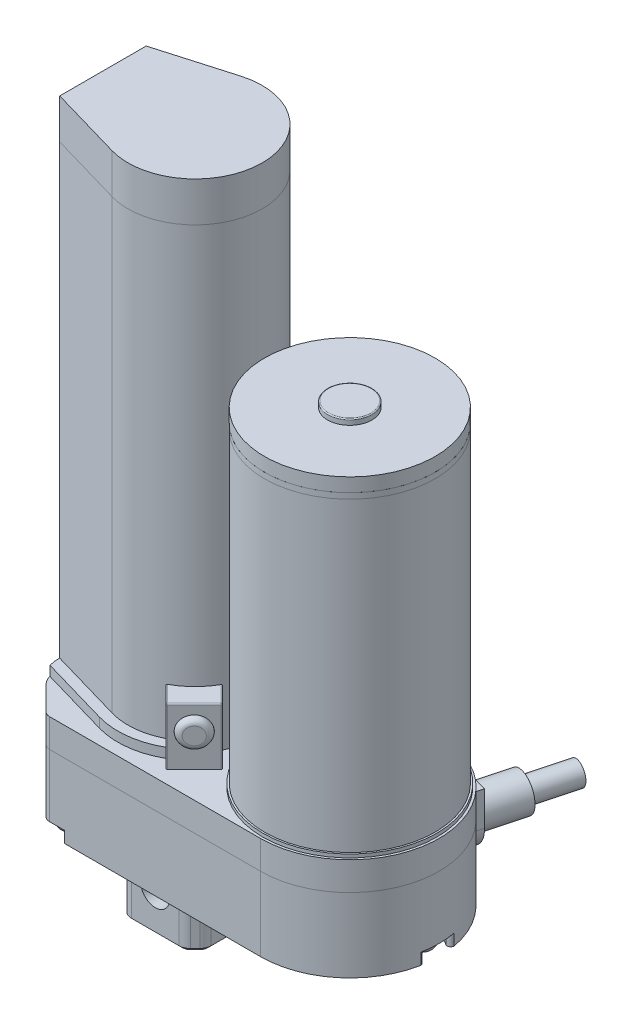
SolidWorks part; units mm, degrees
note: '?' marks a value the reader was unsure of. The reader was unsure of these and kept them because the rebuilt part matched: shared geometry of "Sketch1<3>", "Sketch41<11>", "Sketch41<12>", "Sketch45<3>".
ref_plane "Front Plane" through (0, 0, 0) normal (0, 0, 1) x (1, 0, 0)
ref_plane "Top Plane" through (0, 0, 0) normal (0, 1, 0) x (1, 0, 0)
ref_plane "Right Plane" through (0, 0, 0) normal (1, 0, 0) x (0, 0, -1)
sketch "Sketch1" plane through (0, 0, 0) normal (0, 1, 0) x (1, 0, 0)
  line L0 (0, 32.639) -> (7.239, 39.878)
  line L1 (7.239, 0) -> (55.118, 0)
  line L2 (0, 7.239) -> (0, 32.639)
  line L3 (7.239, 39.878) -> (55.118, 39.878)
  line L4 (7.239, 0) -> (0, 7.239)
  arc A0 (55.118, 0) -> (55.118, 39.878) centre (55.118, 19.939) ccw
  point P0 (0, 0)
  point P2 (0, 39.878)
  dimension "D1" = 55.118
  dimension "D2" = 39.878
extrude "Boss-Extrude1" add sketch "Sketch1" along normal blind 6.35
sketch "Sketch6" plane through (0, 6.35, 0) normal (0, 1, 0) x (1, 0, 0)
  circle A0 centre (55.118, 19.939) radius 19.431
extrude "Boss-Extrude4" add sketch "Sketch6" along normal blind 0.762 separate body contours A0
sketch "Sketch7" plane through (0, 7.112, 0) normal (0, 1, 0) x (1, 0, 0)
  circle A0 centre (55.118, 19.939) radius 19.05
  dimension "D1" = 38.1
extrude "Boss-Extrude5" add sketch "Sketch7" along normal blind 68.326 separate body
sketch "Sketch8" plane through (0, 75.438, 0) normal (0, 1, 0) x (1, 0, 0)
  circle A0 centre (55.118, 19.939) radius 4.953
  dimension "D1" = 9.906
fillet "Fillet6" radius 5.08 2 edges at (0, 3.175, -7.239) (0, 3.175, -32.639)
fillet "Fillet7" radius 1.905 2 edges at (7.239, 3.175, -39.878) (7.239, 3.175, 0)
sketch "Sketch15" plane through (0, 6.35, 0) normal (0, 1, 0) x (1, 0, 0)
  line L0 (35.5603, 29.0153) -> (35.5603, 29.0265)
  line L2 (0, 30.5348) -> (0, 9.3432) construction
  line L3 (0, 19.939) -> (0, 10.2869)
  line L4 (0, 19.939) -> (0, 29.591)
  line L5 (0, 10.2869) -> (16.412, 5.5423)
  line L7 (35.5603, 10.8628) -> (35.5603, 10.8515)
  line L10 (0, 29.591) -> (16.4119, 34.3357)
  arc A0 (16.412, 5.5423) -> (16.4119, 34.3357) centre (20.574, 19.939) ccw
ref_plane "Plane4" through (13.8375, 0, -51.6424) normal (0.2588, 0, -0.9659) x (0, -1, 0)
ref_plane "Plane5" through (12.5227, 0, -46.7355) normal (0.2588, 0, -0.9659) x (0, -1, 0)
sketch "Sketch23" plane through (12.5227, 0, -46.7355) normal (0.2588, 0, -0.9659) x (0, -1, 0)
  line L0 (-6.35, -67.5103) -> (-6.35, -28.6483) construction
  line L1 (-2.032, -53.8839) -> (5.588, -53.8839)
  line L2 (-2.032, -53.8839) -> (-2.032, -42.4539)
  line L3 (-2.032, -42.4539) -> (5.588, -42.4539)
  arc A0 (5.588, -53.8839) -> (5.588, -42.4539) centre (5.588, -48.1689) ccw
  dimension "D1" = 11.43
  dimension "D2" = 7.62
  dimension "D3" = 4.318
extrude "Boss-Extrude15" add sketch "Sketch23" along normal blind 6.35
sketch "Sketch24" plane through (14.1662, 0, -52.8692) normal (0.2588, 0, -0.9659) x (-0.9659, 0, -0.2588)
  circle A0 centre (-48.1689, -5.588) radius 4.064
  dimension "D1" = 8.128
extrude "Boss-Extrude16" add sketch "Sketch24" along normal blind 10.16
sketch "Sketch25" plane through (16.7959, 0, -62.683) normal (0.2588, 0, -0.9659) x (-0.9659, 0, -0.2588)
  circle A0 centre (-48.1689, -5.588) radius 2.54
  dimension "D1" = 5.08
extrude "Boss-Extrude17" add sketch "Sketch25" along normal blind 10.16
extrude "Boss-Extrude19" add sketch "Sketch1<3>" against normal blind 16.51 separate body
sketch "Sketch1<3>" plane through (0, 0, 0) normal (0, 1, 0) x (1, 0, 0) same geometry as "Sketch1"
fillet "Fillet13" radius 1.905 2 edges at (7.239, -8.255, 0) (7.239, -8.255, -39.878)
fillet "Fillet14" radius 5.08 2 edges at (0, -8.255, -32.639) (0, -8.255, -7.239)
sketch "Sketch26" plane through (0, -16.51, 0) normal (0, -1, 0) x (-1, 0, 0)
  line L4 (-20.574, 28.829) -> (-11.684, 28.829)
  line L5 (-20.574, 28.829) -> (-29.464, 28.829)
  line L6 (-11.684, 28.829) -> (-11.684, 11.049)
  line L7 (-11.684, 11.049) -> (-29.464, 11.049)
  line L8 (-29.464, 11.049) -> (-29.464, 28.829)
extrude "Boss-Extrude20" add sketch "Sketch26" along normal blind 18.796 separate body
chamfer "Chamfer1" distance 2.54 angle 45 4 edges at (29.464, -25.908, -28.829) (29.464, -25.908, -11.049) (11.684, -25.908, -11.049) (11.684, -25.908, -28.829)
fillet "Fillet15" radius 2.54 8 edges at (11.684, -25.908, -13.589) (14.224, -25.908, -11.049) (26.924, -25.908, -11.049) (29.464, -25.908, -13.589) (29.464, -25.908, -26.289) (26.924, -25.908, -28.829) (11.684, -25.908, -26.289) (14.224, -25.908, -28.829)
chamfer "Chamfer2" distance 0.762 angle 45 16 edges at (14.3041, -35.306, -11.2423) (20.574, -35.306, -11.049) (26.8439, -35.306, -11.2423) (28.194, -35.306, -12.319) (29.2707, -35.306, -13.6691) (29.464, -35.306, -19.939) (29.2707, -35.306, -26.2089) (28.194, -35.306, -27.559) (26.8439, -35.306, -28.6357) (20.574, -35.306, -28.829) (14.3041, -35.306, -28.6357) (12.954, -35.306, -27.559) (11.8773, -35.306, -26.2089) (11.684, -35.306, -19.939) (11.8773, -35.306, -13.6691) (12.954, -35.306, -12.319)
sketch "Sketch27" plane through (0, 0, -11.049) normal (0, 0, 1) x (1, 0, 0)
  circle A0 centre (20.574, -26.67) radius 3.175
extrude "Cut-Extrude3" cut sketch "Sketch27" against normal blind 19.05
sketch "Sketch28" plane through (0, 75.438, 0) normal (0, 1, 0) x (1, 0, 0)
  circle A0 centre (55.118, 19.939) radius 19.05
extrude "Boss-Extrude22" add sketch "Sketch28" along normal blind 1.27 separate body
sketch "Sketch29" plane through (0, 76.708, 0) normal (0, 1, 0) x (1, 0, 0)
  circle A0 centre (55.118, 19.939) radius 19.05
extrude "Boss-Extrude24" add sketch "Sketch29" along normal blind 3.048 separate body contours A0
extrude "Boss-Extrude25" add sketch "Sketch8" along normal blind 1.27 from surface at 4.318 contours A0 starting at face at (55.118, 79.756, -0.889)
fillet "Fillet16" radius 0.2286 1 edges at (55.118, 81.026, -14.986)
extrude "Boss-Extrude26" add sketch "Sketch15" along normal blind 101.981 separate body contours L5 A0 L10 L4 L3
sketch "Sketch32" plane through (0, 108.331, 0) normal (0, 1, 0) x (1, 0, 0)
  line L0 (0, 10.2869) -> (0, 29.591)
  line L1 (0, 29.591) -> (16.4119, 34.3357)
  line L2 (0, 10.2869) -> (16.412, 5.5423)
  arc A0 (16.412, 5.5423) -> (16.4119, 34.3357) centre (20.574, 19.939) ccw
extrude "Boss-Extrude27" add sketch "Sketch32" along normal blind 8.89 separate body
sketch "Sketch33" plane through (0, 117.221, 0) normal (0, 1, 0) x (1, 0, 0)
  circle A0 centre (20.574, 19.939) radius 9.906
extrude "Boss-Extrude28" add sketch "Sketch33" along normal blind 21.336
sketch3d "3DSketch1" plane through (0, 0, 0) normal (0, 0, 1) x (1, 0, 0)
sketch "Sketch41" plane through (0, 6.35, 0) normal (0, 1, 0) x (1, 0, 0)
  line L0 (16.4119, 34.3357) -> (0, 29.591)
  line L1 (37.5429, 9.0662) -> (33.7712, 12.8379)
  line L2 (0.2737, 32.0497) -> (15.777, 36.5318)
  line L3 (37.5429, 9.0662) -> (31.2567, 2.78)
  line L4 (0, 29.591) -> (0, 30.5348)
  line L5 (0, 30.5348) -> (0.2737, 32.0497)
  line L6 (-0.6349, 31.7871) -> (15.777, 36.5318) construction
  line L7 (0, 19.9389) -> (7.9017, 19.9389)
  line L8 (31.2567, 2.78) -> (27.426, 6.6107)
  line L9 (0, 10.2869) -> (0, 29.591) construction
  line L10 (0, 10.2869) -> (0, 9.3431)
  line L12 (37.5429, 30.8116) -> (33.7712, 27.0399)
  line L13 (37.5429, 30.8116) -> (31.2567, 37.0978)
  line L14 (31.2567, 37.0978) -> (27.426, 33.2671)
  line L15 (0, 9.3431) -> (0.2737, 7.8281)
  line L16 (0.2737, 7.8281) -> (15.777, 3.3461)
  line L17 (16.4119, 5.5422) -> (0, 10.2869)
  line L18 (-0.6349, 8.0908) -> (15.7771, 3.3462) construction
  line L19 (27.426, 33.2671) -> (29.1122, 34.9533)
  line L20 (0, 29.591) -> (16.4119, 34.3357) construction
  line L21 (0, 10.2869) -> (16.412, 5.5423) construction
  arc A0 (16.4119, 34.3357) -> (33.7712, 27.0399) centre (20.574, 19.939) cw
  arc A1 (15.777, 36.5318) -> (29.1122, 34.9533) centre (20.574, 19.939) cw
  arc A2 (16.4119, 34.3357) -> (16.412, 5.5423) centre (20.574, 19.939) cw construction
  arc A3 (15.777, 36.5318) -> (15.7771, 3.3462) centre (20.574, 19.939) cw construction
  arc A4 (16.4119, 34.3357) -> (27.426, 33.2671) centre (20.574, 19.939) cw
  arc A5 (15.777, 3.3461) -> (29.1122, 4.9245) centre (20.574, 19.9389) ccw
  arc A6 (16.4119, 5.5422) -> (33.7712, 12.8379) centre (20.574, 19.9389) ccw
  line M5 (0, 30.5348) -> (0, 9.3432)
  arc M6 (0, 9.3432) -> (1.4879, 5.7511) centre (5.08, 9.3432) ccw
extrude "Boss-Extrude30" add sketch "Sketch41" along normal blind 2.159 separate body contours A1 L2 L5 L0 A0 L14 M5
extrude "Boss-Extrude31" add sketch "Sketch41<11>" along normal blind 2.159 separate body contours A6 L17 L15 L16 A5 L8 M5 M6
sketch "Sketch41<11>" plane through (0, 6.35, 0) normal (0, 1, 0) x (1, 0, 0) same geometry as "Sketch41"
extrude "Boss-Extrude33" add sketch "Sketch41<12>" along normal blind 12.7 separate body contours L14 A0 L12 L13 | A6 L8 L3 L1
sketch "Sketch41<12>" plane through (0, 6.35, 0) normal (0, 1, 0) x (1, 0, 0) same geometry as "Sketch41"
fillet "Fillet17" radius 0.2286 5 edges at (35.657, 19.05, -28.9258) (29.3413, 19.05, -35.1825) (34.3998, 19.05, -33.9547) (37.5429, 12.7, -30.8116) (31.2567, 12.7, -37.0978)
fillet "Fillet18" radius 0.2286 5 edges at (35.657, 19.05, -10.9521) (29.3413, 19.05, -4.6954) (37.5429, 12.7, -9.0662) (34.3998, 19.05, -5.9231) (31.2567, 12.7, -2.78)
sketch "Sketch43" plane through (34.1773, 0, -34.1773) normal (0.7071, 0, -0.7071) x (-0.7071, 0, -0.7071)
  circle A0 centre (-0.3147, 13.7414) radius 3.175
extrude "Boss-Extrude34" add sketch "Sketch43" along normal blind 1.27 separate body
fillet "Fillet19" radius 1.27 1 edges at (33.0527, 13.7414, -37.0978)
sketch "Sketch44" plane through (14.2383, 0, 14.2383) normal (0.7071, 0, 0.7071) x (0.7071, 0, -0.7071)
  circle A0 centre (28.5126, 13.7414) radius 3.175
extrude "Boss-Extrude35" add sketch "Sketch44" along normal blind 1.27 separate body
fillet "Fillet20" radius 1.27 1 edges at (37.5429, 13.7414, -7.2702)
sketch "Sketch45" plane through (0, -16.51, 0) normal (0, -1, 0) x (1, 0, 0)
  line L0 (4.0845, -36.7235) -> (6.681, -39.32)
  line L2 (6.681, -39.32) -> (1.4879, -34.1269) construction
  line L4 (55.118, -39.878) -> (8.0281, -39.878) construction
  line L5 (11.3938, -39.878) -> (8.0281, -39.878)
  line L6 (11.3938, 0) -> (8.0281, 0)
  line L7 (4.0845, -3.1545) -> (6.681, -0.558)
  arc A0 (11.2821, -38.9146) -> (11.3938, -39.878) centre (11.8197, -39.3405) ccw
  arc A1 (11.2821, -38.9146) -> (5.0443, -35.9783) centre (8.8543, -35.9783) ccw
  arc A2 (11.2821, -0.9634) -> (11.3938, 0) centre (11.8197, -0.5375) cw
  arc A3 (5.0443, -35.9783) -> (4.0845, -36.7235) centre (4.1918, -35.871) cw
  arc A4 (5.0443, -3.8997) -> (4.0845, -3.1545) centre (4.1918, -4.007) ccw
  arc A5 (11.2821, -0.9634) -> (5.0443, -3.8997) centre (8.8543, -3.8997) cw
  arc A6 (55.118, -39.878) -> (55.118, 0) centre (55.118, -19.939) ccw construction
  arc A7 (73.6621, -16.9922) -> (73.6621, -22.8858) centre (71.247, -19.939) ccw
  arc A8 (73.6621, -22.8858) -> (74.7121, -23.6317) centre (73.8141, -23.7837) cw
  arc A9 (73.6621, -16.9922) -> (74.7121, -16.2463) centre (73.8141, -16.0943) ccw
  arc A10 (8.0281, -39.878) -> (6.681, -39.32) centre (8.0281, -37.973) cw
  arc A11 (8.0281, 0) -> (6.681, -0.558) centre (8.0281, -1.905) ccw
  arc A12 (74.7121, -23.6317) -> (74.7121, -16.2463) centre (55.118, -19.939) ccw
  line M8 (1.4879, -34.1269) -> (6.681, -39.32)
  arc M9 (6.681, -39.32) -> (8.0281, -39.878) centre (8.0281, -37.973) ccw
  line M10 (8.0281, -39.878) -> (55.118, -39.878)
  line M12 (55.118, 0) -> (8.0281, 0)
  arc M13 (8.0281, 0) -> (6.681, -0.558) centre (8.0281, -1.905) ccw
  line M14 (6.681, -0.558) -> (1.4879, -5.7511)
extrude "Cut-Extrude5" cut sketch "Sketch45" against normal blind 2.54 contours A1 A3 A0 M8 M9 M10 | A5 A2 A4 M12 M13 M14
extrude "Cut-Extrude6" cut sketch "Sketch45<3>" against normal blind 2.54
sketch "Sketch45<3>" plane through (0, -16.51, 0) normal (0, -1, 0) x (1, 0, 0) same geometry as "Sketch45"
sketch "Sketch47" plane through (0, -13.97, 0) normal (0, -1, 0) x (-1, 0, 0)
  circle A0 centre (-8.8543, 35.9783) radius 2.54
  circle A1 centre (-8.8543, 3.8997) radius 2.54
  circle A2 centre (-71.247, 19.939) radius 2.54
extrude "Boss-Extrude36" add sketch "Sketch47" along normal blind 2.54 separate body
fillet "Fillet22" radius 1.524 1 edges at (8.8543, -16.51, -38.5183)
fillet "Fillet23" radius 1.524 1 edges at (8.8543, -16.51, -6.4397)
sketch "Sketch48" plane through (0, 0, 0) normal (-1, 0, 0) x (0, 0, 1)
  circle A0 centre (-19.939, 12.7) radius 3.81
extrude "Boss-Extrude37" add sketch "Sketch48" along normal blind 1.524
fillet "Fillet24" radius 1.524 1 edges at (-1.524, 12.7, -16.129)
fillet "Fillet25" radius 1.524 1 edges at (71.247, -16.51, -22.479)
sketch "Sketch49" plane through (0, 0, 0) normal (-1, 0, 0) x (0, 0, 1)
  line L0 (-19.9389, 108.331) -> (-19.9389, 103.378) construction
  line L1 (-29.591, 108.331) -> (-10.2869, 108.331) construction
  line L2 (-30.5348, 6.35) -> (-9.3432, 6.35) construction
  circle A0 centre (-19.9389, 103.378) radius 3.81
  dimension "Flat Head Screw" = 97.028
extrude "Cut-Extrude7" cut sketch "Sketch49" against normal blind 2.54
sketch "Sketch50" plane through (2.54, 0, 0) normal (-1, 0, 0) x (0, 0, 1)
  circle A0 centre (-19.9389, 103.378) radius 3.556
extrude "Boss-Extrude39" add sketch "Sketch50" along normal blind 2.54 contours A0
sketch "Sketch52" plane through (0, 0, -11.049) normal (0, 0, 1) x (1, 0, 0)
  circle A0 centre (20.574, 129.032) radius 3.175
  circle A1 centre (20.574, -26.67) radius 3.175 construction
  dimension "Hole to Hole" = 155.702
extrude "Cut-Extrude11" cut sketch "Sketch52" against normal through all both and the other way through all
sketch "Sketch54" plane through (0, 138.557, 0) normal (0, 1, 0) x (1, 0, 0)
  circle A1 centre (20.574, 19.939) radius 9.906
  circle A2 centre (20.574, 19.939) radius 9.906
  dimension "D1" = 0
extrude "Cut-Extrude12" cut sketch "Sketch54" against normal blind 21.336
ref_axis "Axis1" through (20.574, 151.9514, -19.939) along (0, -1, 0)?
equation "\"Stroke\"= 2in"
equation "\"D1@Boss-Extrude26\"= \"Stroke\" + 2.015"
equation "\"Flat Head Screw@Sketch49\"= \"Stroke\" + 1.82"
equation "\"Hole to Hole@Sketch52\"= \"Stroke\" + 4.13"
